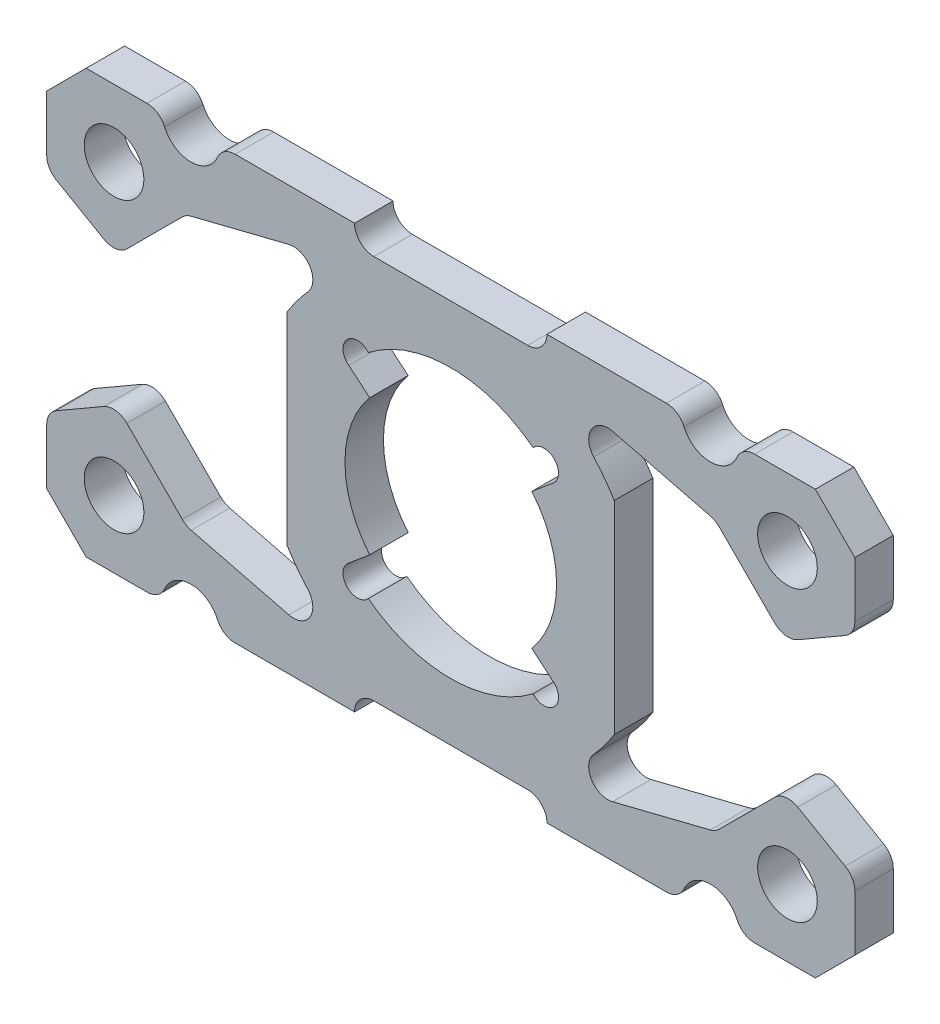
SolidWorks part; units mm, degrees
ref_plane "前视基准面" through (0, 0, 0) normal (0, 0, 1) x (1, 0, 0)
ref_plane "上视基准面" through (0, 0, 0) normal (0, 1, 0) x (1, 0, 0)
ref_plane "右视基准面" through (0, 0, 0) normal (1, 0, 0) x (0, 0, -1)
sketch "草图1" plane through (0, 0, 0) normal (0, 0, 1) x (1, 0, 0)
  line L0 (-21, 8.9497) -> (-21, -8.9497)
  line L1 (17.5, -7.5) -> (-17.5, -7.5) construction
  line L2 (17.5, -7.5) -> (17.5, 7.5) construction
  line L3 (17.5, 7.5) -> (-17.5, 7.5) construction
  line L4 (-17.5, -7.5) -> (-17.5, 7.5) construction
  line L5 (17.5, -7.5) -> (-17.5, 7.5) construction
  line L6 (17.5, 7.5) -> (-17.5, -7.5) construction
  line L7 (-21, -8.9497) -> (-18.9497, -11)
  line L8 (-18.9497, -11) -> (18.9497, -11)
  line L9 (18.9497, -11) -> (21, -8.9497)
  line L10 (21, -8.9497) -> (21, 8.9497)
  line L11 (21, 8.9497) -> (18.9497, 11)
  line L12 (18.9497, 11) -> (-18.9497, 11)
  line L13 (-18.9497, 11) -> (-21, 8.9497)
  circle A0 centre (-17.5, 7.5) radius 1.55
  circle A1 centre (-17.5, -7.5) radius 1.55
  circle A2 centre (17.5, -7.5) radius 1.55
  circle A3 centre (17.5, 7.5) radius 1.55
  circle A4 centre (0, 0) radius 7
  circle A6 centre (-17.5, 7.5) radius 3.5 construction
  circle A7 centre (-17.5, -7.5) radius 3.5 construction
  circle A8 centre (17.5, -7.5) radius 3.5 construction
  circle A9 centre (17.5, 7.5) radius 3.5 construction
  point P0 (0, 0)
  dimension "D3" = 3.1
  dimension "D4" = 14
  dimension "D6" = 7
  dimension "D1" = 35
  dimension "D2" = 15
  dimension "D7" = 45
  dimension "D8" = 135
  dimension "D9" = 45
  dimension "D10" = 45
extrude "凸台-拉伸1" add sketch "草图1" along normal mid plane 2
sketch "草图2" plane through (0, 0, 1) normal (0, 0, 1) x (1, 0, 0)
  line L0 (-21, 5.4793) -> (-19.5, 4.6132)
  line L1 (-21, 8.9497) -> (-21, -8.9497) construction
  line L2 (-19.5, 4.6132) -> (-19.5, -4.6132)
  line L3 (-19.5, -4.6132) -> (-21, -5.4793)
  line L4 (-21, -5.4793) -> (-21, 5.4793)
  line L5 (-17, 3.7574) -> (-17, -3.7574)
  line L6 (-17, -3.7574) -> (-13.7574, -7)
  line L7 (-13.7574, -7) -> (-7.7574, -8.5)
  line L8 (-7.7574, -8.5) -> (-5.2678, -8.5)
  line L10 (-5.2678, 8.5) -> (-7.7574, 8.5)
  line L11 (-7.7574, 8.5) -> (-13.7574, 7)
  line L12 (-13.7574, 7) -> (-17, 3.7574)
  line L13 (-21, -8.9497) -> (-18.9497, -11) construction
  line L14 (-18.9497, 11) -> (-21, 8.9497) construction
  line L15 (-18.9497, -11) -> (18.9497, -11) construction
  circle A0 centre (-17.5, 7.5) radius 1.55 construction
  circle A1 centre (-17.5, -7.5) radius 1.55 construction
  arc A2 (-5.2678, 8.5) -> (-5.2678, -8.5) centre (0, 0) ccw
  circle A3 centre (0, 0) radius 7 construction
  point P21 (-19.5, 0)
  dimension "D4" = 3
  dimension "D8" = 3
  dimension "D1" = 1.5
  dimension "D2" = 60
  dimension "D3" = 3.5
  dimension "D5" = 3
  dimension "D6" = 2.5
  dimension "D7" = 2.5
  dimension "D9" = 6
  dimension "D10" = 1.5
extrude "切除-拉伸1" cut sketch "草图2" against normal through all
fillet "圆角1" radius 1 8 edges at (-19.5, 4.6132, 0) (-19.5, -4.6132, 0) (-5.2678, -8.5, 0) (-13.7574, -7, 0) (-17, -3.7574, 0) (-17, 3.7574, 0) (-13.7574, 7, 0) (-5.2678, 8.5, 0)
sketch "草图3" plane through (0, 0, 1) normal (0, 0, 1) x (1, 0, 0)
  line L0 (18.9497, 11) -> (-18.9497, 11) construction
  line L1 (-18.9497, -11) -> (18.9497, -11) construction
  line L2 (-13.5, -11) -> (-13.5, 11) construction
  circle A0 centre (-13.5, 11) radius 1.5
  circle A1 centre (-13.5, -11) radius 1.5
  circle A2 centre (-17.5, 7.5) radius 1.55 construction
  dimension "D1" = 4
  dimension "D2" = 3
extrude "切除-拉伸2" cut sketch "草图3" against normal through all
fillet "圆角2" radius 1 4 edges at (-12, 11, 0) (-15, 11, 0) (-12, -11, 0) (-15, -11, 0)
mirror "镜向1" about plane through (0, 0, 0) normal (1, 0, 0) of "切除-拉伸1", "圆角1", "圆角2", "切除-拉伸2"
sketch "草图4" plane through (0, 0, 1) normal (0, 0, 1) x (1, 0, 0)
  line L1 (-4, 11) -> (4, 11) construction
  line L2 (11.2087, 11) -> (-11.2087, 11) construction
  line L3 (-4, 12) -> (4, 12)
  line L4 (-4, 10) -> (4, 10)
  arc A1 (-4, 12) -> (-4, 10) centre (-4, 11) ccw
  arc A2 (4, 10) -> (4, 12) centre (4, 11) ccw
  point P4 (0, 11)
  dimension "D1" = 1
  dimension "D2" = 8
extrude "切除-拉伸3" cut sketch "草图4" against normal through all
mirror "镜向2" about plane through (0, 0, 0) normal (0, 1, 0) of "切除-拉伸3"
fillet "圆角3" radius 1 4 edges at (7.7574, 8.5, 0) (7.7574, -8.5, 0) (-7.7574, -8.5, 0) (-7.7574, 8.5, 0)
sketch "草图5" plane through (0, 0, 1) normal (0, 0, 1) x (1, 0, 0)
  line L0 (-5.3623, 4.4995) -> (-4.2132, 3.5353)
  line L1 (-5.3623, -4.4995) -> (-4.2132, -3.5353)
  line L2 (4.2132, 3.5353) -> (5.3623, 4.4995)
  line L3 (4.2132, -3.5353) -> (5.3623, -4.4995)
  arc A0 (4.2132, -3.5353) -> (4.2132, 3.5353) centre (0, 0) ccw
  circle A1 centre (0, 0) radius 7 construction
  arc A2 (5.3623, -4.4995) -> (5.3623, 4.4995) centre (0, 0) ccw
  arc A3 (-4.2132, 3.5353) -> (-4.2132, -3.5353) centre (0, 0) ccw
  arc A4 (-5.3623, 4.4995) -> (-5.3623, -4.4995) centre (0, 0) ccw
  dimension "D1" = 11
  dimension "D2" = 80
extrude "凸台-拉伸2" add sketch "草图5" against normal up to surface (2 mm away) up to face at (0, 0, -1)
sketch "草图6" plane through (0, 0, 1) normal (0, 0, 1) x (1, 0, 0)
  circle A0 centre (-4.8501, 5.0474) radius 0.75
  arc A1 (5.3623, 4.4995) -> (-5.3623, 4.4995) centre (0, 0) ccw construction
  circle A2 centre (-4.8501, -5.0474) radius 0.75
  arc A3 (-5.3623, -4.4995) -> (5.3623, -4.4995) centre (0, 0) ccw construction
  dimension "D1" = 1.5
extrude "切除-拉伸4" cut sketch "草图6" against normal through all
mirror "镜向3" about plane through (0, 0, 0) normal (1, 0, 0) of "切除-拉伸4"
sketch "草图7" plane through (0, 0, 1) normal (0, 0, 1) x (1, 0, 0)
  line L0 (-8.5, 5.2678) -> (-8.5, -5.2678)
  line L1 (8.5, 5.2678) -> (8.5, -5.2678)
  arc A0 (-7.4267, 6.6966) -> (-7.4267, -6.6966) centre (0, 0) ccw construction
  arc A1 (7.4267, -6.6966) -> (7.4267, 6.6966) centre (0, 0) ccw construction
  arc A2 (8.5, -5.2678) -> (8.5, 5.2678) centre (0, 0) ccw
  arc A3 (-8.5, 5.2678) -> (-8.5, -5.2678) centre (0, 0) ccw
  dimension "D1" = 17
extrude "切除-拉伸5" cut sketch "草图7" against normal through all
sketch "草图8" plane through (0, 0, 1) normal (0, 0, 1) x (1, 0, 0)
  line L0 (-20, 4.9019) -> (-17.3725, 3.3849)
  line L1 (-20, 4.9019) -> (-21, 5.4793) construction
  line L2 (-17.3725, 3.3849) -> (-16.7071, 4.0503)
  line L3 (-13.9532, 6.8041) -> (-16.7071, 4.0503) construction
  line L4 (-20, -4.9019) -> (-17.3725, -3.3849)
  line L5 (-17.3725, -3.3849) -> (-16.7071, -4.0503)
  line L6 (-16.7071, -4.0503) -> (-13.9532, -6.8041) construction
  line L7 (-21, -5.4793) -> (-20, -4.9019) construction
  line L8 (-17, 3.3431) -> (-17, -3.3431) construction
  line L9 (-19.5, -4.0359) -> (-19.5, 4.0359) construction
  line L10 (-17, 3.3431) -> (-17, -3.3431)
  line L11 (-19.5, -4.0359) -> (-19.5, 4.0359)
  arc A0 (-17, -3.3431) -> (-16.7071, -4.0503) centre (-16, -3.3431) ccw construction
  arc A1 (-16.7071, 4.0503) -> (-17, 3.3431) centre (-16, 3.3431) ccw construction
  arc A2 (-20, -4.9019) -> (-19.5, -4.0359) centre (-20.5, -4.0359) ccw construction
  arc A3 (-19.5, 4.0359) -> (-20, 4.9019) centre (-20.5, 4.0359) ccw construction
  arc A4 (-16.7071, 4.0503) -> (-17, 3.3431) centre (-16, 3.3431) ccw
  arc A5 (-17, -3.3431) -> (-16.7071, -4.0503) centre (-16, -3.3431) ccw
  arc A6 (-20, -4.9019) -> (-19.5, -4.0359) centre (-20.5, -4.0359) ccw
  arc A7 (-19.5, 4.0359) -> (-20, 4.9019) centre (-20.5, 4.0359) ccw
extrude "切除-拉伸6" cut sketch "草图8" against normal through all
mirror "镜向4" about plane through (0, 0, 0) normal (1, 0, 0) of "切除-拉伸6"
fillet "圆角4" radius 1 8 edges at (21, -5.4793, 0) (17.3725, -3.3849, 0) (21, 5.4793, 0) (17.3725, 3.3849, 0) (-21, 5.4793, 0) (-21, -5.4793, 0) (-17.3725, -3.3849, 0) (-17.3725, 3.3849, 0)
